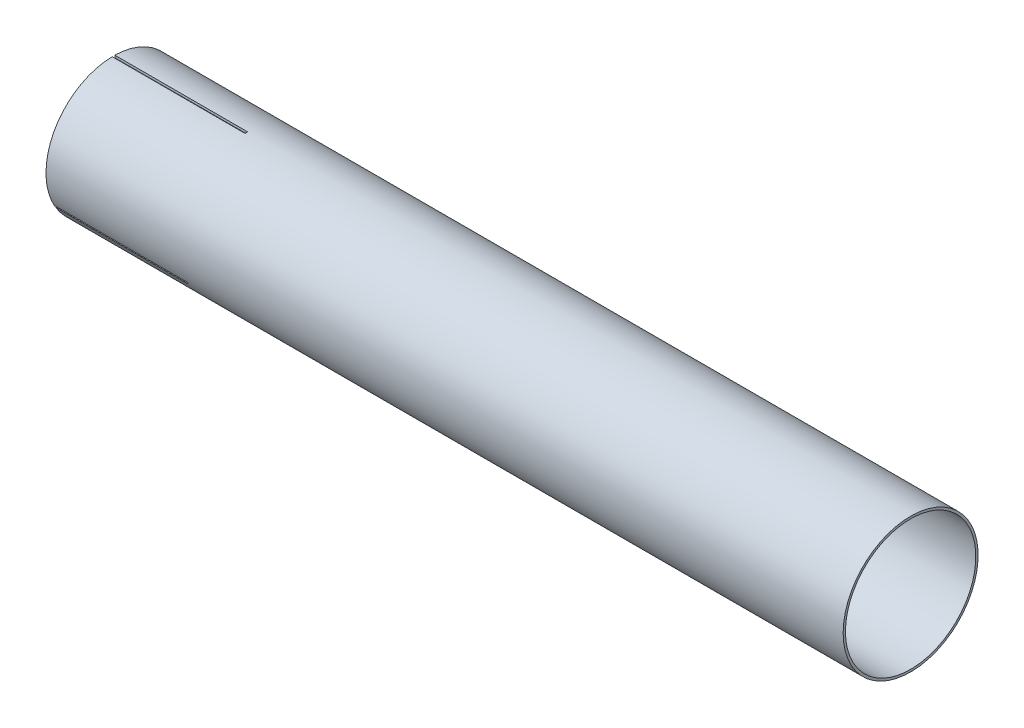
SolidWorks part; units mm, degrees
ref_plane "Plan de face" through (0, 0, 0) normal (0, 0, 1) x (1, 0, 0)
ref_plane "Plan de dessus" through (0, 0, 0) normal (0, 1, 0) x (1, 0, 0)
ref_plane "Plan de droite" through (0, 0, 0) normal (1, 0, 0) x (0, 0, -1)
sketch "Esquisse1" plane through (0, 0, 0) normal (0, 0, 1) x (1, 0, 0)
  line L0 (0, 0) -> (0, 76.2) construction
  line L1 (0, 0) -> (142.5133, 0) construction
  line L2 (0, 76.2) -> (900, 76.2)
  line L3 (0, 76.2) -> (0, -76.2) construction
  line L4 (0, 73.6092) -> (900, 73.6092)
  line L5 (900, 76.2) -> (900, 73.6092)
  line L6 (0, -76.2) -> (900, -76.2) construction
  line L7 (0, 76.2) -> (0, 73.6092)
  dimension "D1" = 152.4
  dimension "D2" = 2.5908
  dimension "D3" = 900
revolve "Révolution1" add sketch "Esquisse1" angle 360 about L1
sketch "Esquisse2" plane through (0, 0, 0) normal (0, 1, 0) x (1, 0, 0)
  line L0 (0, 76.2) -> (0, -76.2) construction
  line L1 (0, -1.5) -> (150, -1.5)
  line L2 (0, -1.5) -> (0, 1.5)
  line L3 (0, 1.5) -> (150, 1.5)
  line L4 (150, -1.5) -> (150, 1.5)
  dimension "D1" = 3
  dimension "D2" = 150
extrude "Enlèv. mat.-Extru.1" cut sketch "Esquisse2" along normal through all
pattern_circular "Répétition circulaire1" count 3 over 240 about axis through (900, 0, 0) along (-1, 0, 0) of "Enlèv. mat.-Extru.1"
